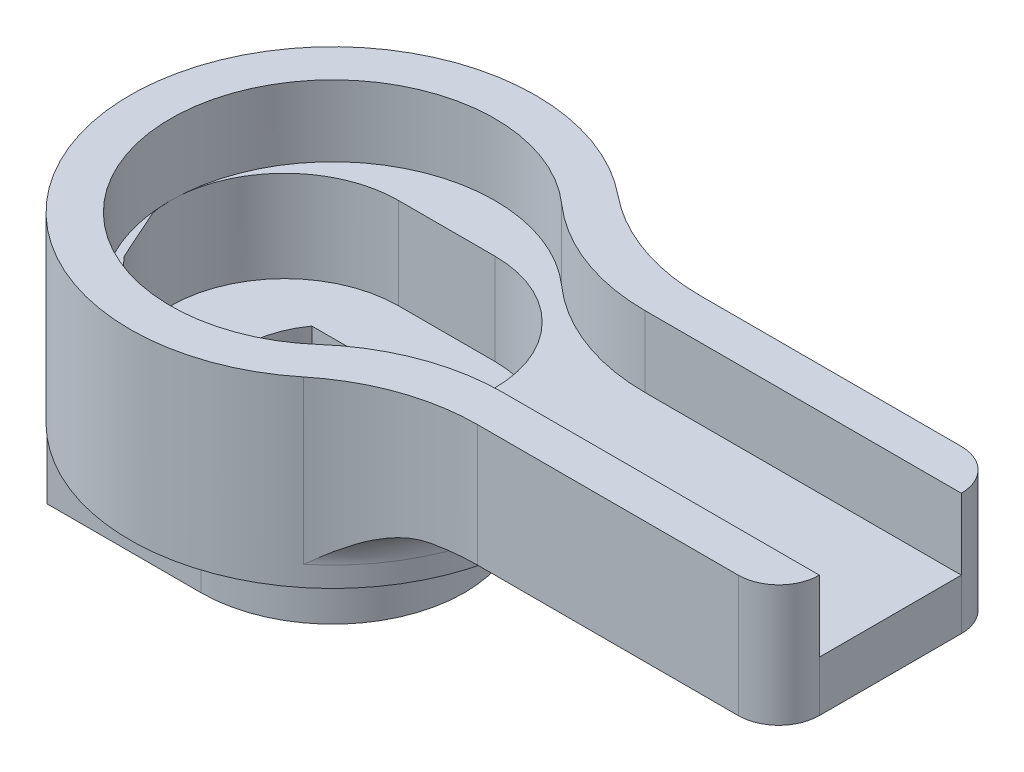
SolidWorks part; units mm, degrees
ref_plane "Front Plane" through (0, 0, 0) normal (0, 0, 1) x (1, 0, 0)
ref_plane "Top Plane" through (0, 0, 0) normal (0, 1, 0) x (1, 0, 0)
ref_plane "Right Plane" through (0, 0, 0) normal (1, 0, 0) x (0, 0, -1)
sketch "Sketch1" plane through (0, 0, 0) normal (0, 1, 0) x (1, 0, 0)
  circle A0 centre (0, 0) radius 6.5
extrude "Boss-Extrude1" add sketch "Sketch1" along normal blind 8
sketch "Sketch14" plane through (0, 8, 0) normal (0, 1, 0) x (1, 0, 0)
  circle A0 centre (0, 0) radius 10
extrude "Boss-Extrude6" add sketch "Sketch14" against normal blind 4
sketch "Sketch15" plane through (0, 8, 0) normal (0, 1, 0) x (1, 0, 0)
  circle A0 centre (0, 0) radius 5.625
extrude "Cut-Extrude7" cut sketch "Sketch15" against normal blind 3
sketch "Sketch2" plane through (0, 0, 0) normal (0, 1, 0) x (1, 0, 0)
  circle A0 centre (0, 0) radius 4.5
extrude "Cut-Extrude1" cut sketch "Sketch2" along normal up to next
sketch "Sketch3" plane through (0, 0, 0) normal (0, 1, 0) x (1, 0, 0)
  line L1 (-5.0382, -2.625) -> (5.0382, -2.625)
  line L2 (-5.0382, -2.625) -> (-5.0382, 2.625) construction
  line L3 (-5.0382, 2.625) -> (5.0382, 2.625)
  line L4 (5.0382, -2.625) -> (5.0382, 2.625) construction
  line L5 (-5.0382, -2.625) -> (5.0382, 2.625) construction
  line L6 (-5.0382, 2.625) -> (5.0382, -2.625) construction
  arc A0 (-5.0382, 2.625) -> (5.0382, 2.625) centre (0, 0) cw
  arc A1 (-5.0382, -2.625) -> (5.0382, -2.625) centre (0, 0) ccw
  point P0 (0, 0)
  dimension "D1" = 5.25
extrude "Boss-Extrude2" add sketch "Sketch3" along normal blind 8
sketch "Sketch4" plane through (0, 8, 0) normal (0, 1, 0) x (1, 0, 0)
  circle A0 centre (0, 0) radius 10
extrude "Boss-Extrude3" add sketch "Sketch4" along normal blind 5
sketch "Sketch6" plane through (0, 13, 0) normal (0, 1, 0) x (1, 0, 0)
  line L0 (27.5, -5.5) -> (-7.5, -5.5)
  line L1 (27.5, -5.5) -> (27.5, 5.5)
  line L2 (-7.5, -5.5) -> (-7.5, 5.5)
  line L3 (27.5, 5.5) -> (-7.5, 5.5)
  line L4 (27.5, -5.5) -> (-7.5, 5.5) construction
  line L5 (-7.5, -5.5) -> (27.5, 5.5) construction
  point P1 (10, 0)
  dimension "D1" = 11
  dimension "D2" = 35
extrude "Boss-Extrude4" add sketch "Sketch6" against normal blind 6
sketch "Sketch7" plane through (0, 13, 0) normal (0, 1, 0) x (1, 0, 0)
  circle A0 centre (0, 0) radius 8
extrude "Cut-Extrude2" cut sketch "Sketch7" against normal blind 3.5
sketch "Sketch8" plane through (0, 13, 0) normal (0, 1, 0) x (1, 0, 0)
  line L0 (29.1729, -3.5) -> (-0.8271, -3.5)
  line L1 (29.1729, -3.5) -> (29.1729, 3.5)
  line L2 (-0.8271, -3.5) -> (-0.8271, 3.5)
  line L3 (29.1729, 3.5) -> (-0.8271, 3.5)
  line L4 (29.1729, -3.5) -> (-0.8271, 3.5) construction
  line L5 (-0.8271, -3.5) -> (29.1729, 3.5) construction
  point P0 (0, 0)
  point P1 (14.1729, 0)
  dimension "D1" = 7
  dimension "D2" = 30
extrude "Cut-Extrude3" cut sketch "Sketch8" against normal blind 3.5
fillet "Fillet1" radius 10 4 edges at (7.1937, 11.25, 3.5) (7.1937, 11.25, -3.5) (8.3516, 10, 5.5) (8.3516, 10, -5.5)
fillet "Fillet2" radius 2 2 edges at (27.5, 10, 5.5) (27.5, 10, -5.5)
sketch "Sketch9" plane through (0, 9.5, 0) normal (0, 1, 0) x (1, 0, 0)
  line L0 (0, 0) -> (20, 0) construction
  line L1 (20, 0) -> (24, 0) construction
  circle A0 centre (20, 0) radius 1.5
  circle A1 centre (24, 0) radius 1.5
extrude "Cut-Extrude4" cut sketch "Sketch9" against normal up to next
sketch "Sketch16" plane through (0, 9.5, 0) normal (0, 1, 0) x (1, 0, 0)
  line L0 (-2.375, 0) -> (2.375, 0) construction
  line L1 (-2.375, 5.625) -> (2.375, 5.625)
  line L2 (-2.375, -5.625) -> (2.375, -5.625)
  arc A1 (-2.375, 5.625) -> (-2.375, -5.625) centre (-2.375, 0) ccw
  arc A2 (2.375, -5.625) -> (2.375, 5.625) centre (2.375, 0) ccw
  point P3 (0, 0)
extrude "Cut-Extrude8" cut sketch "Sketch16" against normal up to vertex (4.5 mm away) up to point (-3.655, 5, -2.625)
sketch "Sketch19" plane through (0, 4, 0) normal (0, -1, 0) x (1, 0, 0)
  line L2 (0, 6.5) -> (0, 6)
  line L4 (0, 6.5) -> (-7.5993, 6.5)
  line L5 (0, -6.5) -> (-7.5993, -6.5)
  line L6 (0, -6.5) -> (0, -6)
  circle A0 centre (0, 0) radius 6.5 construction
  arc A1 (-7.5993, -6.5) -> (-7.5993, 6.5) centre (0, 0) cw
  circle A2 centre (0, 0) radius 6.5 construction
  arc A7 (0, 6) -> (0, -6) centre (0, 0) ccw
  circle A8 centre (0, 0) radius 10 construction
extrude "Boss-Extrude7" add sketch "Sketch19" along normal up to surface (4 mm away) up to face at (0, 0, 0)
fillet "Fillet4" radius 2 1 edges at (10, 7, 0)
